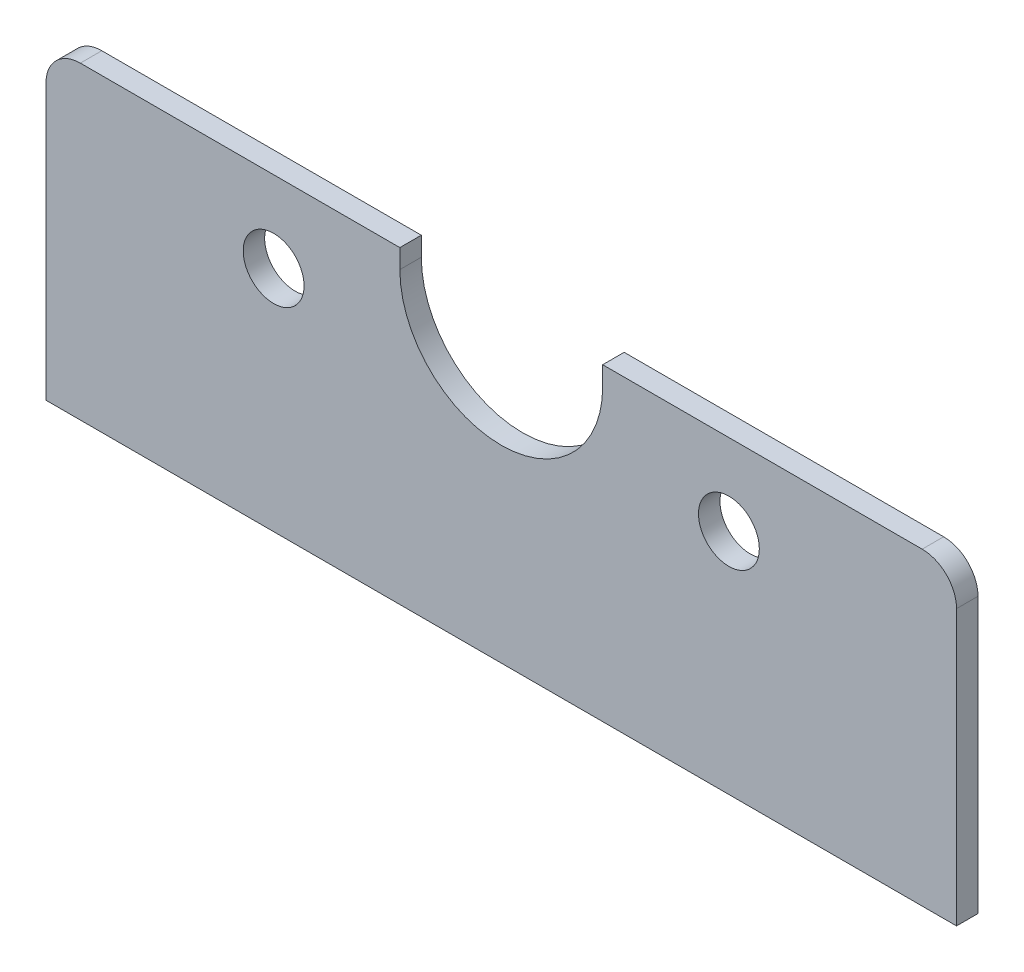
SolidWorks part; units mm, degrees
material "Custom Plastic"
ref_plane "X-Y Datum" through (0, 0, 0) normal (0, 0, 1) x (1, 0, 0)
ref_plane "X-Z Datum" through (0, 0, 0) normal (0, 1, 0) x (1, 0, 0)
ref_plane "Y-Z Datum" through (0, 0, 0) normal (1, 0, 0) x (0, 0, -1)
sketch "Sketch1" plane through (0, 0, 0) normal (0, 0, 1) x (1, 0, 0)
  line L5 (-21.1688, 18.0128) -> (-21.1688, 34.0128) construction
  line L18 (46.1632, 18.0128) -> (46.1632, 34.0128) construction
  line L19 (46.1632, 18.0128) -> (-21.1688, 18.0128) construction
  line L20 (6.9972, 34.0128) -> (6.9972, 30.6031) construction
  line L21 (-21.1688, 34.0128) -> (6.9972, 34.0128) construction
  line L22 (17.9972, 34.0128) -> (46.1632, 34.0128) construction
  line L23 (17.9972, 30.6031) -> (17.9972, 34.0128) construction
  line L24 (46.1632, 18.0128) -> (46.1632, 34.0128) construction
  line L25 (46.1632, 18.0128) -> (-21.1688, 18.0128) construction
  line L26 (-21.1688, 18.0128) -> (-21.1688, 34.0128) construction
  line L27 (-21.1688, 32.0128) -> (4.9972, 32.0128)
  line L28 (4.9972, 32.0128) -> (4.9972, 30.6031)
  line L29 (19.9972, 30.6031) -> (19.9972, 32.0128)
  line L30 (19.9972, 32.0128) -> (46.1632, 32.0128)
  line L31 (19.9972, 32.0128) -> (46.1632, 32.0128)
  line L32 (-21.1688, 32.0128) -> (4.9972, 32.0128)
  line L33 (-21.1688, 32.0128) -> (-21.1688, 9.1528)
  line L34 (-21.1688, 9.1528) -> (46.1632, 9.1528)
  line L35 (46.1632, 32.0128) -> (46.1632, 9.1528)
  circle A5 centre (-4.3358, 26.0128) radius 3.025 construction
  circle A6 centre (29.3302, 26.0128) radius 3.025 construction
  circle A8 centre (-4.3358, 26.0128) radius 3.025 construction
  circle A9 centre (29.3302, 26.0128) radius 3.025 construction
  arc A10 (6.9972, 30.6031) -> (17.9972, 30.6031) centre (12.4972, 30.6031) ccw construction
  arc A11 (4.9972, 30.6031) -> (19.9972, 30.6031) centre (12.4972, 30.6031) ccw
  dimension "D2" = 22.86
  dimension "D1" = 2
extrude "Boss-Extrude1" add sketch "Sketch1" along normal blind 1.5875 contours A11 L28 L27 L33 L34 L35 L30 L29 region at (12.4972, 20.0016, 0)
hole_wizard "M4 Clearance Hole1" positions "Sketch2" profile "Sketch3" hole size "M4" standard "ANSI Metric" end condition through all
sketch "Sketch2" plane through (0, 0, 1.5875) normal (0, 0, 1) x (1, 0, 0)
  point P2 (-4.3358, 26.0128)
  point P5 (29.3302, 26.0128)
  point P9 (0, 0)
sketch "Sketch3" plane through (-4.3358, 26.0128, 1.5875) normal (1, 0, 0) x (0, -1, 0)
  line L0 (0, 0) -> (0, 1.5875)
  line L1 (0, 1.5875) -> (2.25, 1.5875)
  line L2 (2.25, 1.5875) -> (2.25, 0)
  line L5 (2.25, 0) -> (0, 0)
  line L11 (0, -6.35) -> (0, 107.95) construction
  dimension "Thru Hole Dia." = 4.5
  dimension "Thru Hole Depth" = 1.5875
fillet "Fillet1" radius 2.54 2 edges at (46.1632, 32.0128, 0.7937) (-21.1688, 32.0128, 0.7937)
